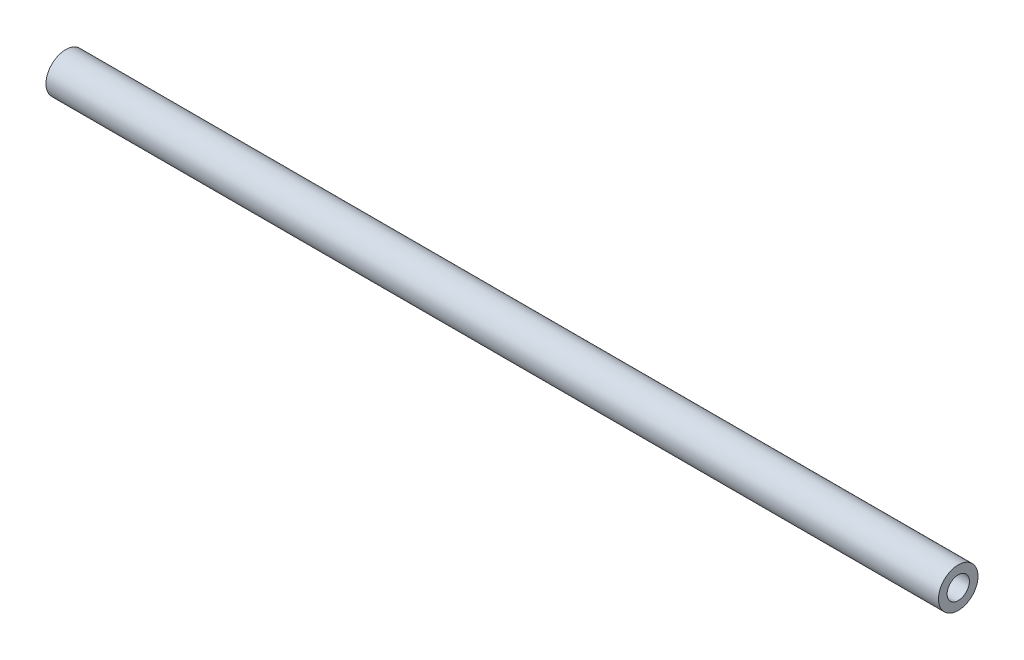
SolidWorks part; units mm, degrees
ref_plane "Front Plane" through (0, 0, 0) normal (0, 0, 1) x (1, 0, 0)
ref_plane "Top Plane" through (0, 0, 0) normal (0, 1, 0) x (1, 0, 0)
ref_plane "Right Plane" through (0, 0, 0) normal (1, 0, 0) x (0, 0, -1)
sketch "Sketch1" plane through (0, 0, 0) normal (1, 0, 0) x (0, 0, -1)
  circle A0 centre (0, 0) radius 1.55
  dimension "D1" = 3.1
extrude "Boss-Extrude1" add sketch "Sketch1" along normal blind 35 and the other way blind 35
hole_wizard "M2x0.25 Tapped Hole1" positions "Sketch2" profile "Sketch3" tap size "M2x0.25" standard "DIN"
sketch "Sketch2" plane through (35, 0, 0) normal (1, 0, 0) x (0, 0, -1)
  point P0 (0, 0)
cosmetic thread "Hole Thread1" parameters "D2"=2
sketch "Sketch3" plane through (35, 0, 0) normal (0, 1, 0) x (0, 0, -1)
  line L0 (0, 0) -> (0, 10.5258)
  line L1 (0, 10.5258) -> (0.875, 10)
  line L2 (0.875, 10) -> (0.875, 0)
  line L5 (0.875, 0) -> (0, 0)
  line L10 (0, 10.5258) -> (-0.875, 10) construction
  line L11 (0, -6.35) -> (0, 107.95) construction
  dimension "Tap Drill Dia." = 1.75
  dimension "Tap Drill Depth" = 10
  dimension "Drill Angle" = 118
mirror "Mirror1" about plane through (0, 0, 0) normal (1, 0, 0) of "M2x0.25 Tapped Hole1"
cosmetic thread "Hole Thread2" parameters "D1"=70, "D2"=2
